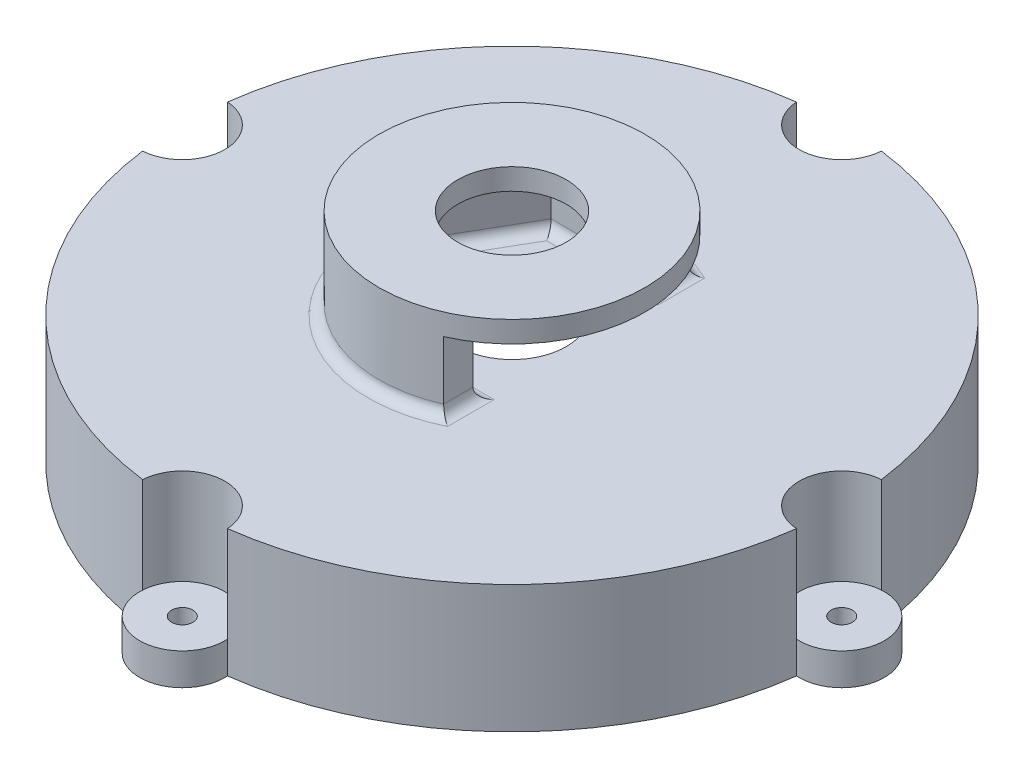
SolidWorks part; units mm, degrees
ref_plane "Front Plane" through (0, 0, 0) normal (0, 0, 1) x (1, 0, 0)
ref_plane "Top Plane" through (0, 0, 0) normal (0, 1, 0) x (1, 0, 0)
ref_plane "Right Plane" through (0, 0, 0) normal (1, 0, 0) x (0, 0, -1)
sketch "Sketch1" plane through (0, 0, 0) normal (0, 1, 0) x (1, 0, 0)
  circle A0 centre (0, 0) radius 26
  circle A1 centre (0, 0) radius 25 construction
  circle A2 centre (0, 31) radius 1
  circle A3 centre (0, 31) radius 4
  arc A4 (-3.9917, 30.7419) -> (-30.7419, 3.9917) centre (0, 0) ccw
  circle A5 centre (31, 0) radius 4
  circle A6 centre (31, 0) radius 1
  circle A7 centre (0, -31) radius 4
  circle A8 centre (0, -31) radius 1
  circle A9 centre (-31, 0) radius 4
  circle A10 centre (-31, 0) radius 1
  arc A11 (-30.7419, -3.9917) -> (-3.9917, -30.7419) centre (0, 0) ccw
  arc A12 (3.9917, -30.7419) -> (30.7419, -3.9917) centre (0, 0) ccw
  arc A13 (30.7419, 3.9917) -> (3.9917, 30.7419) centre (0, 0) ccw
  point P23 (0, 0)
sketch "Sketch2" plane through (0, 0, 0) normal (0, 1, 0) x (1, 0, 0)
  circle A0 centre (0, 31) radius 1 construction
  circle A1 centre (0, 31) radius 4 construction
  arc A2 (30.7419, 3.9917) -> (3.9917, 30.7419) centre (0, 0) ccw construction
  circle A3 centre (31, 0) radius 4 construction
  circle A4 centre (31, 0) radius 1 construction
  circle A5 centre (0, -31) radius 1 construction
  arc A6 (3.9917, -30.7419) -> (30.7419, -3.9917) centre (0, 0) ccw construction
  circle A7 centre (0, -31) radius 4 construction
  circle A8 centre (-31, 0) radius 1 construction
  circle A9 centre (-31, 0) radius 4 construction
  arc A10 (-30.7419, -3.9917) -> (-3.9917, -30.7419) centre (0, 0) ccw construction
  circle A11 centre (0, 0) radius 26 construction
  arc A12 (-3.9917, 30.7419) -> (-30.7419, 3.9917) centre (0, 0) ccw construction
  circle A13 centre (0, 31) radius 1
  arc A14 (3.9917, 30.7419) -> (-3.9917, 30.7419) centre (0, 31) ccw
  arc A15 (30.7419, 3.9917) -> (3.9917, 30.7419) centre (0, 0) ccw
  arc A16 (30.7419, -3.9917) -> (30.7419, 3.9917) centre (31, 0) ccw
  circle A17 centre (31, 0) radius 1
  circle A18 centre (0, -31) radius 1
  arc A19 (3.9917, -30.7419) -> (30.7419, -3.9917) centre (0, 0) ccw
  arc A20 (-3.9917, -30.7419) -> (3.9917, -30.7419) centre (0, -31) ccw
  circle A21 centre (-31, 0) radius 1
  arc A22 (-30.7419, 3.9917) -> (-30.7419, -3.9917) centre (-31, 0) ccw
  arc A23 (-30.7419, -3.9917) -> (-3.9917, -30.7419) centre (0, 0) ccw
  circle A24 centre (0, 0) radius 26
  arc A25 (-3.9917, 30.7419) -> (-30.7419, 3.9917) centre (0, 0) ccw
extrude "Boss-Extrude1" add sketch "Sketch2" along normal blind 10
sketch "Sketch3" plane through (0, 10, 0) normal (0, 1, 0) x (1, 0, 0)
  circle A0 centre (0, 0) radius 31
  circle A1 centre (0, 0) radius 5.1
  arc A2 (30.7419, 3.9917) -> (3.9917, 30.7419) centre (0, 0) ccw construction
  dimension "D1" = 10.2
extrude "Boss-Extrude2" add sketch "Sketch3" along normal blind 2
sketch "Sketch4" plane through (0, 12, 0) normal (0, 1, 0) x (1, 0, 0)
  line L0 (-5.0229, 8.7) -> (-10.0459, 0)
  line L1 (-4.9075, 8.5) -> (-9.815, 0) construction
  line L2 (-9.815, 0) -> (-4.9075, -8.5) construction
  line L3 (-4.9075, -8.5) -> (4.9075, -8.5) construction
  line L4 (4.9075, -8.5) -> (9.815, 0) construction
  line L5 (9.815, 0) -> (4.9075, 8.5) construction
  line L6 (4.9075, 8.5) -> (-4.9075, 8.5) construction
  line L7 (-10.0459, 0) -> (-5.0229, -8.7)
  line L8 (-5.0229, -8.7) -> (5.0229, -8.7)
  line L11 (5.0229, 8.7) -> (-5.0229, 8.7)
  line L12 (-6.1776, 10.7) -> (-12.3553, 0)
  line L13 (-12.3553, 0) -> (-6.1776, -10.7)
  line L14 (-6.1776, -10.7) -> (5.0229, -10.7)
  line L17 (5.0229, 10.7) -> (-6.1776, 10.7)
  line L18 (12.3553, 0) -> (6.1776, 10.7) construction
  line L19 (6.1776, -10.7) -> (12.3553, 0) construction
  line L20 (5.0229, -8.7) -> (5.0229, -10.7)
  line L21 (5.0229, 8.7) -> (5.0229, 10.7)
  line L22 (6.1776, 10.7) -> (-6.1776, 10.7) construction
  line L23 (-6.1776, -10.7) -> (6.1776, -10.7) construction
  line L24 (10.0459, 0) -> (5.0229, 8.7) construction
  line L25 (5.0229, -8.7) -> (10.0459, 0) construction
  circle A0 centre (0, 0) radius 8.5 construction
  dimension "D1" = 17
  dimension "D2" = 0.2
  dimension "D3" = 2
extrude "Boss-Extrude3" add sketch "Sketch4" along normal blind 6.5
sketch "Sketch5" plane through (0, 18.5, 0) normal (0, 1, 0) x (1, 0, 0)
  circle A0 centre (0, 0) radius 12.5
  circle A1 centre (0, 0) radius 5.1
  circle A2 centre (0, 0) radius 5.1 construction
  dimension "D1" = 25
extrude "Boss-Extrude4" add sketch "Sketch5" along normal blind 2
fillet "Fillet1" radius 1 9 edges at (0, 12, -8.7) (-7.5344, 12, -4.35) (-7.5344, 12, 4.35) (0, 12, 8.7) (0, 18.5, 8.7) (-7.5344, 18.5, 4.35) (-7.5344, 18.5, -4.35) (-10.0459, 15.25, 0) (0, 18.5, -8.7)
sketch "Sketch6" plane through (0, 18.5, 0) normal (0, -1, 0) x (1, 0, 0)
  line L0 (-12.3553, 0) -> (-6.1776, 10.7) construction
  line L1 (-12.3553, 0) -> (-6.1776, 10.7)
  line L2 (-6.1776, -10.7) -> (-12.3553, 0) construction
  line L3 (5.0229, -10.7) -> (-6.1776, -10.7) construction
  line L4 (-6.1776, 10.7) -> (5.0229, 10.7) construction
  line L5 (-6.1776, -10.7) -> (-12.3553, 0)
  line L6 (5.0229, -10.7) -> (-6.1776, -10.7)
  line L7 (-6.1776, 10.7) -> (5.0229, 10.7)
  line L8 (5.0229, 10.7) -> (5.0229, -10.7) construction
  line L9 (5.0229, -11.4464) -> (5.0229, 11.4464)
  circle A1 centre (0, 0) radius 12.5
  arc A2 (5.0229, 11.4464) -> (5.0229, -11.4464) centre (0, 0) ccw
  point P11 (5.0229, 0)
  circle M4 centre (0, 0) radius 12.5
  line M12 (5.0229, -10.7) -> (-6.1776, -10.7)
  line M13 (-6.1776, -10.7) -> (-12.3553, 0)
  line M14 (-12.3553, 0) -> (-6.1776, 10.7)
  line M15 (-6.1776, 10.7) -> (5.0229, 10.7)
  dimension "D1" = 0
extrude "Boss-Extrude5" add sketch "Sketch6" along normal up to surface (6.5 mm away) contours L9 M4 M12 M13 M14 M15 region at (-9.5309, 18.5, -5.5026) up to face at (0, 12, 31)
fillet "Fillet2" radius 1 3 edges at (-12.5, 12, 0) (5.0229, 12, -9.5732) (5.0229, 12, 9.5732)
sketch "Sketch7" plane through (0, 12, 0) normal (0, 1, 0) x (1, 0, 0)
  circle A0 centre (0, -31) radius 4 construction
  circle A1 centre (31, 0) radius 4 construction
  circle A2 centre (0, 31) radius 4 construction
  circle A3 centre (-31, 0) radius 4 construction
  circle A4 centre (0, -31) radius 4
  circle A5 centre (31, 0) radius 4
  circle A6 centre (0, 31) radius 4
  circle A7 centre (-31, 0) radius 4
extrude "Cut-Extrude1" cut sketch "Sketch7" against normal blind 9
sketch "Sketch9" plane through (0, 10, 0) normal (0, -1, 0) x (1, 0, 0)
  circle A0 centre (0, 0) radius 5.1 construction
  circle A1 centre (0, 0) radius 26
  circle A3 centre (0, 0) radius 5.1
  circle A5 centre (0, 0) radius 26
  dimension "D1" = 0
sketch "Sketch10" plane through (0, 10, 0) normal (0, -1, 0) x (1, 0, 0)
  line L2 (-4, 25.6905) -> (-4, 15)
  line L3 (-4, 15) -> (4, 15)
  line L4 (4, 25.6905) -> (4, 15)
  circle A1 centre (0, 0) radius 26
  arc A2 (4, 25.6905) -> (-4, 25.6905) centre (0, 0) ccw
  point P10 (0, 15)
  dimension "D2" = 8
  dimension "D3" = 15
  dimension "D1" = 0
extrude "Boss-Extrude6" add sketch "Sketch10" along normal up to surface (10 mm away) up to face at (0, 0, 0)
pattern_circular "CirPattern1" count 4 over 360 about axis through (0, 10, 0) along (0, 1, 0) of "Boss-Extrude6"
sketch "Sketch11" plane through (0, 10, 0) normal (0, -1, 0) x (1, 0, 0)
  line L0 (-25.3969, 4.25) -> (-14.75, 4.25)
  line L1 (-14.75, 4.25) -> (-14.75, -4.25)
  line L2 (-14.75, -4.25) -> (-25.3969, -4.25)
  line L3 (-4.25, -25.3969) -> (-4.25, -14.75)
  line L4 (-4.25, -14.75) -> (4.25, -14.75)
  line L5 (4.25, -14.75) -> (4.25, -25.3969)
  line L6 (25.3969, -4.25) -> (14.75, -4.25)
  line L7 (14.75, -4.25) -> (14.75, 4.25)
  line L8 (14.75, 4.25) -> (25.3969, 4.25)
  line L9 (4.25, 25.3969) -> (4.25, 14.75)
  line L10 (4.25, 14.75) -> (-4.25, 14.75)
  line L11 (-4.25, 14.75) -> (-4.25, 25.3969)
  line L12 (-25.6905, 4) -> (-15, 4)
  line L13 (-15, 4) -> (-15, -4)
  line L14 (-15, -4) -> (-25.6905, -4)
  line L15 (-4, -25.6905) -> (-4, -15)
  line L16 (-4, -15) -> (4, -15)
  line L17 (4, -15) -> (4, -25.6905)
  line L18 (25.6905, -4) -> (15, -4)
  line L19 (15, -4) -> (15, 4)
  line L20 (15, 4) -> (25.6905, 4)
  line L21 (4, 25.6905) -> (4, 15)
  line L22 (4, 15) -> (-4, 15)
  line L23 (-4, 15) -> (-4, 25.6905)
  line L24 (-25.6905, 4) -> (-15, 4) construction
  line L25 (-15, 4) -> (-15, -4) construction
  line L26 (-15, -4) -> (-25.6905, -4) construction
  line L27 (-4, -25.6905) -> (-4, -15) construction
  line L28 (-4, -15) -> (4, -15) construction
  line L29 (4, -15) -> (4, -25.6905) construction
  line L30 (25.6905, -4) -> (15, -4) construction
  line L31 (15, -4) -> (15, 4) construction
  line L32 (15, 4) -> (25.6905, 4) construction
  line L33 (4, 25.6905) -> (4, 15) construction
  line L34 (4, 15) -> (-4, 15) construction
  line L35 (-4, 15) -> (-4, 25.6905) construction
  arc A0 (-25.3969, -4.25) -> (-4.25, -25.3969) centre (0, 0) ccw
  arc A1 (4.25, -25.3969) -> (25.3969, -4.25) centre (0, 0) ccw
  arc A2 (25.3969, 4.25) -> (4.25, 25.3969) centre (0, 0) ccw
  arc A3 (-4.25, 25.3969) -> (-25.3969, 4.25) centre (0, 0) ccw
  arc A4 (-25.6905, -4) -> (-4, -25.6905) centre (0, 0) ccw
  arc A5 (4, -25.6905) -> (25.6905, -4) centre (0, 0) ccw
  arc A6 (25.6905, 4) -> (4, 25.6905) centre (0, 0) ccw
  arc A7 (-4, 25.6905) -> (-25.6905, 4) centre (0, 0) ccw
  arc A8 (-25.6905, -4) -> (-4, -25.6905) centre (0, 0) ccw construction
  arc A9 (4, -25.6905) -> (25.6905, -4) centre (0, 0) ccw construction
  arc A10 (25.6905, 4) -> (4, 25.6905) centre (0, 0) ccw construction
  arc A11 (-4, 25.6905) -> (-25.6905, 4) centre (0, 0) ccw construction
  circle A12 centre (0, 0) radius 5.1 construction
  circle A13 centre (0, 0) radius 5.1
  dimension "D1" = 0
  dimension "D2" = 0.25
sketch "Sketch12" plane through (0, 0, 0) normal (0, -1, 0) x (1, 0, 0)
  circle A0 centre (0, 0) radius 26
extrude "Cut-Extrude2" cut sketch "Sketch12" against normal blind 3
